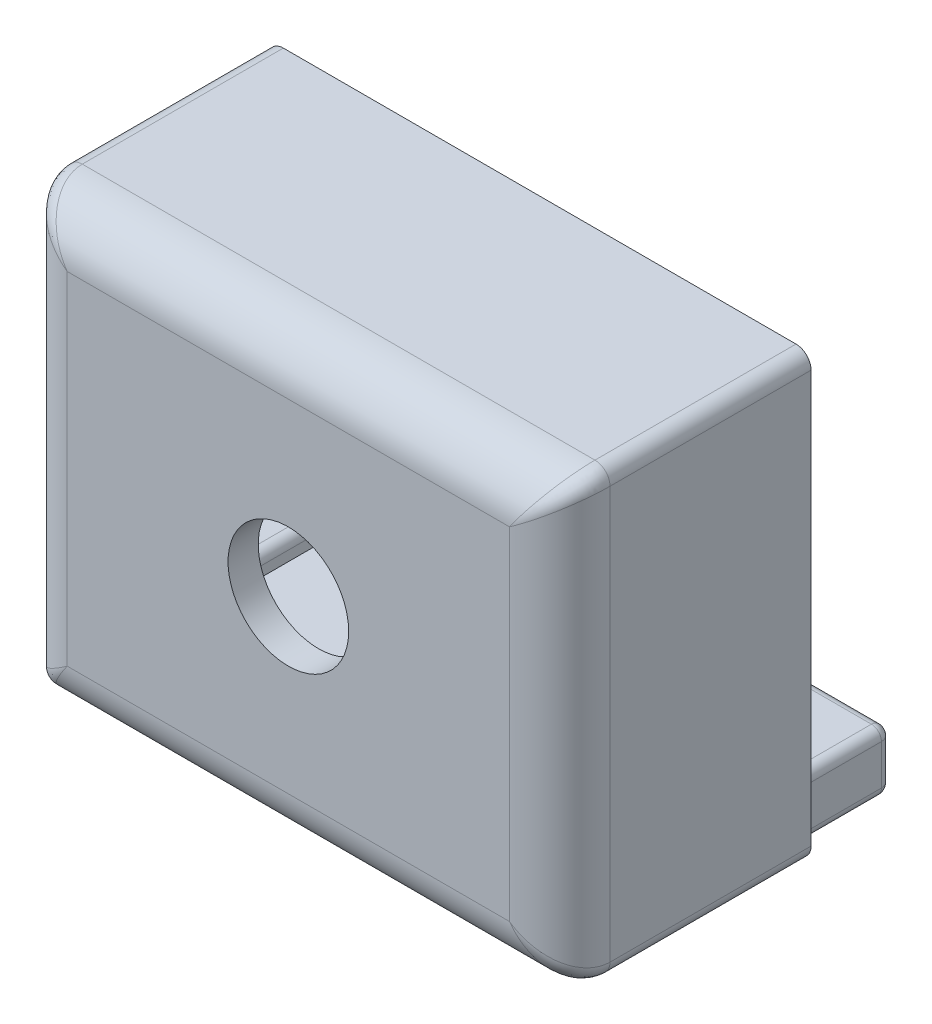
SolidWorks part; units mm, degrees
ref_plane "Front Plane" through (0, 0, 0) normal (0, 0, 1) x (1, 0, 0)
ref_plane "Top Plane" through (0, 0, 0) normal (0, 1, 0) x (1, 0, 0)
ref_plane "Right Plane" through (0, 0, 0) normal (1, 0, 0) x (0, 0, -1)
sketch "Sketch1" plane through (0, 0, 0) normal (0, 0, 1) x (1, 0, 0)
  line L0 (-11.5, 0) -> (11.5, 0) construction
  line L1 (-24.5, 13) -> (25.5, -27) construction
  line L2 (-11.5, 0) -> (-11.5, -7) construction
  line L3 (-11.5, -7) -> (0.5, -7) construction
  line L5 (-24.5, 13) -> (25.5, 13)
  line L6 (-24.5, 13) -> (-24.5, -27)
  line L7 (-24.5, -27) -> (25.5, -27)
  line L8 (25.5, 13) -> (25.5, -27)
  circle A0 centre (-11.5, 0) radius 2 construction
  circle A1 centre (11.5, 0) radius 2 construction
  circle A2 centre (-11.5, 0) radius 0.5 construction
  circle A3 centre (11.5, 0) radius 0.5 construction
  circle A4 centre (0.5, -7) radius 6
  point P0 (0, 0)
  point P17 (0.5, -7)
  dimension "D4" = 4
  dimension "D2" = 1
  dimension "D6" = 12
  dimension "D1" = 23
  dimension "D3" = 7
  dimension "D5" = 12
  dimension "D8" = 50
  dimension "D9" = 40
extrude "Boss-Extrude1" add sketch "Sketch1" along normal mid plane 3
sketch "Sketch2" plane through (0, 0, -1.5) normal (0, 0, -1) x (-1, 0, 0)
  circle A0 centre (-11.5, 0) radius 2
  circle A1 centre (11.5, 0) radius 2
  circle A2 centre (-11.5, 0) radius 0.5
  circle A3 centre (11.5, 0) radius 0.5
extrude "Boss-Extrude2" add sketch "Sketch2" along normal blind 13
sketch "Sketch3" plane through (0, 0, 1.5) normal (0, 0, 1) x (1, 0, 0)
  line L0 (-26.5, 15) -> (-26.5, -29)
  line L1 (-24.5, 13) -> (25.5, 13)
  line L2 (-24.5, 13) -> (-24.5, -27)
  line L3 (-24.5, -27) -> (25.5, -27)
  line L4 (25.5, 13) -> (25.5, -27)
  line L5 (-26.5, -29) -> (27.5, -29)
  line L6 (27.5, 15) -> (27.5, -29)
  line L7 (-26.5, 15) -> (27.5, 15)
  dimension "D1" = 2
extrude "Boss-Extrude3" add sketch "Sketch3" against normal blind 25
sketch "Sketch4" plane through (0, 0, -23.5) normal (0, 0, -1) x (-1, 0, 0)
  line L0 (-27.5, 12.5) -> (-22.5, 12.5) construction
  line L1 (-27.5, 15) -> (-22.5, 15)
  line L2 (-27.5, 15) -> (-27.5, 10)
  line L3 (-27.5, 10) -> (-23.5, 10)
  line L4 (-22.5, 15) -> (-22.5, 11)
  line L5 (26.5, 15) -> (21.5, 15)
  line L6 (26.5, 15) -> (26.5, 10)
  line L7 (26.5, 10) -> (22.5, 10)
  line L8 (21.5, 15) -> (21.5, 11)
  line L9 (26.5, -29) -> (21.5, -29)
  line L10 (26.5, -29) -> (26.5, -24)
  line L11 (26.5, -24) -> (22.5, -24)
  line L12 (21.5, -29) -> (21.5, -25)
  line L13 (-27.5, -29) -> (-22.5, -29)
  line L14 (-27.5, -29) -> (-27.5, -24)
  line L15 (-27.5, -24) -> (-23.5, -24)
  line L16 (-22.5, -29) -> (-22.5, -25)
  line L17 (-0.5, 15) -> (-0.5, -29) construction
  line L18 (-27.5, 15) -> (26.5, 15) construction
  line L19 (26.5, -29) -> (-27.5, -29) construction
  line L20 (-0.5, -29) -> (-27.5, -7) construction
  line L21 (-27.5, -29) -> (-27.5, 15) construction
  line L22 (-27.5, -7) -> (26.5, -7) construction
  line L23 (26.5, 15) -> (26.5, -29) construction
  arc A0 (-23.5, -24) -> (-22.5, -25) centre (-23.5, -25) cw
  arc A1 (22.5, -24) -> (21.5, -25) centre (22.5, -25) ccw
  arc A2 (22.5, 10) -> (21.5, 11) centre (22.5, 11) cw
  arc A3 (-23.5, 10) -> (-22.5, 11) centre (-23.5, 11) ccw
  circle A4 centre (-25, 12.5) radius 1.6 construction
  circle A5 centre (-25, -26.5) radius 1.6 construction
  circle A6 centre (24, -26.5) radius 1.6 construction
  circle A7 centre (24, 12.5) radius 1.6 construction
  point P28 (-22.5, 10)
  dimension "D3" = 1
  dimension "D4" = 3.2
  dimension "D1" = 5
  dimension "D2" = 5
extrude "Boss-Extrude4" add sketch "Sketch4" against normal blind 12
sketch "Sketch5" plane through (0, 0, -23.5) normal (0, 0, -1) x (-1, 0, 0)
  circle A0 centre (-25, 12.5) radius 1.6
  circle A1 centre (24, 12.5) radius 1.6
  circle A2 centre (24, -26.5) radius 1.5597
  circle A3 centre (-25, -26.5) radius 1.6
extrude "Cut-Extrude1" cut sketch "Sketch5" against normal blind 10
fillet "Fillet1" radius 5 4 edges at (0.5, -29, 1.5) (27.5, -7, 1.5) (0.5, 15, 1.5) (-26.5, -7, 1.5)
fillet "Fillet3" radius 1.5 8 edges at (-25.0355, -27.5355, 0.0355) (26.0355, -27.5355, 0.0355) (-25.0355, 13.5355, 0.0355) (26.0355, 13.5355, 0.0355) (-26.5, -29, -13.5) (27.5, -29, -13.5) (-26.5, 15, -13.5) (27.5, 15, -13.5)
ref_plane "Plane1" through (0, 0, -8.5) normal (0, 0, 1) x (1, 0, 0)
sketch "Sketch6" plane through (0, 0, -8.5) normal (0, 0, 1) x (1, 0, 0)
  line L0 (26, -29) -> (-25, -29) construction
  line L2 (-21.5, -29) -> (-21.5, -32)
  line L3 (-21.5, -32) -> (22.5, -32)
  line L4 (22.5, -29) -> (22.5, -32)
  line L5 (-21.5, -29) -> (-21.5, -26)
  line L6 (-21.5, -26) -> (22.5, -26)
  line L7 (22.5, -26) -> (22.5, -29)
  dimension "D1" = 3
extrude "Boss-Extrude5" add sketch "Sketch6" against normal blind 28
sketch "Sketch7" plane through (0, -26, 0) normal (0, 1, 0) x (1, 0, 0)
  line L0 (0.5, 36.5) -> (0.5, 26.5) construction
  line L1 (22.5, 36.5) -> (-21.5, 36.5) construction
  line L2 (0.5, 31.5) -> (5.5, 31.5) construction
  line L3 (0.5, 31.5) -> (-4.5, 31.5) construction
  circle A0 centre (5.5, 31.5) radius 1.75
  circle A1 centre (-4.5, 31.5) radius 1.75
  point P9 (0, 0)
  dimension "D3" = 3.5
  dimension "D4" = 3.5
  dimension "D5" = 5
  dimension "D6" = 5
  dimension "D7" = 5
  dimension "D1" = 10
  dimension "D2" = 5
extrude "Cut-Extrude2" cut sketch "Sketch7" against normal blind 40
fillet "Fillet8" radius 1 9 edges at (22.5, -29, -16) (-21.5, -29, -16) (0.5, -29, -8.5) (0.5, -32, -8.5) (0.5, -26, -36.5) (-21.5, -32, -22.5) (-21.5, -26, -30) (22.5, -32, -22.5) (22.5, -26, -30)
fillet "Fillet9" radius 1 7 edges at (-21.2071, -26.2929, -36.2071) (-21.2071, -31.7071, -36.5) (0.5, -32, -36.5) (22.2071, -31.7071, -36.5) (22.2071, -26.2929, -36.2071) (-21.5, -29, -36.5) (22.5, -29, -36.5)
